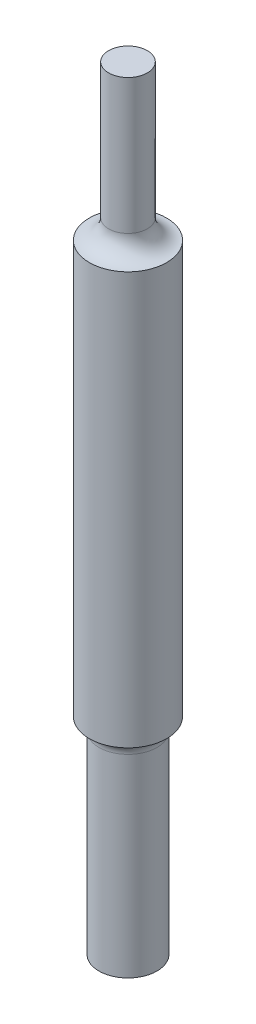
SolidWorks part; units mm, degrees
ref_plane "Front Plane" through (0, 0, 0) normal (0, 0, 1) x (1, 0, 0)
ref_plane "Top Plane" through (0, 0, 0) normal (0, 1, 0) x (1, 0, 0)
ref_plane "Right Plane" through (0, 0, 0) normal (1, 0, 0) x (0, 0, -1)
sketch "Sketch1" plane through (0, 0, 0) normal (0, 1, 0) x (1, 0, 0)
  circle A0 centre (0, 0) radius 19.05
  dimension "D1" = 38.1
extrude "Boss-Extrude1" add sketch "Sketch1" along normal blind 203.2
sketch "Sketch2" plane through (0, 203.2, 0) normal (0, 1, 0) x (1, 0, 0)
  circle A0 centre (0, 0) radius 9.525
  dimension "D1" = 19.05
extrude "Boss-Extrude2" add sketch "Sketch2" along normal blind 76.2
fillet "Fillet1" radius 9.652 1 edges at (0, 203.2, 9.525)
sketch "Sketch3" plane through (0, 0, 0) normal (0, -1, 0) x (1, 0, 0)
  circle A0 centre (0, 0) radius 14.2875
  dimension "D1" = 28.575
extrude "Boss-Extrude3" add sketch "Sketch3" along normal blind 101.6
fillet "Fillet2" radius 6.35 1 edges at (0, 0, 14.2875)
